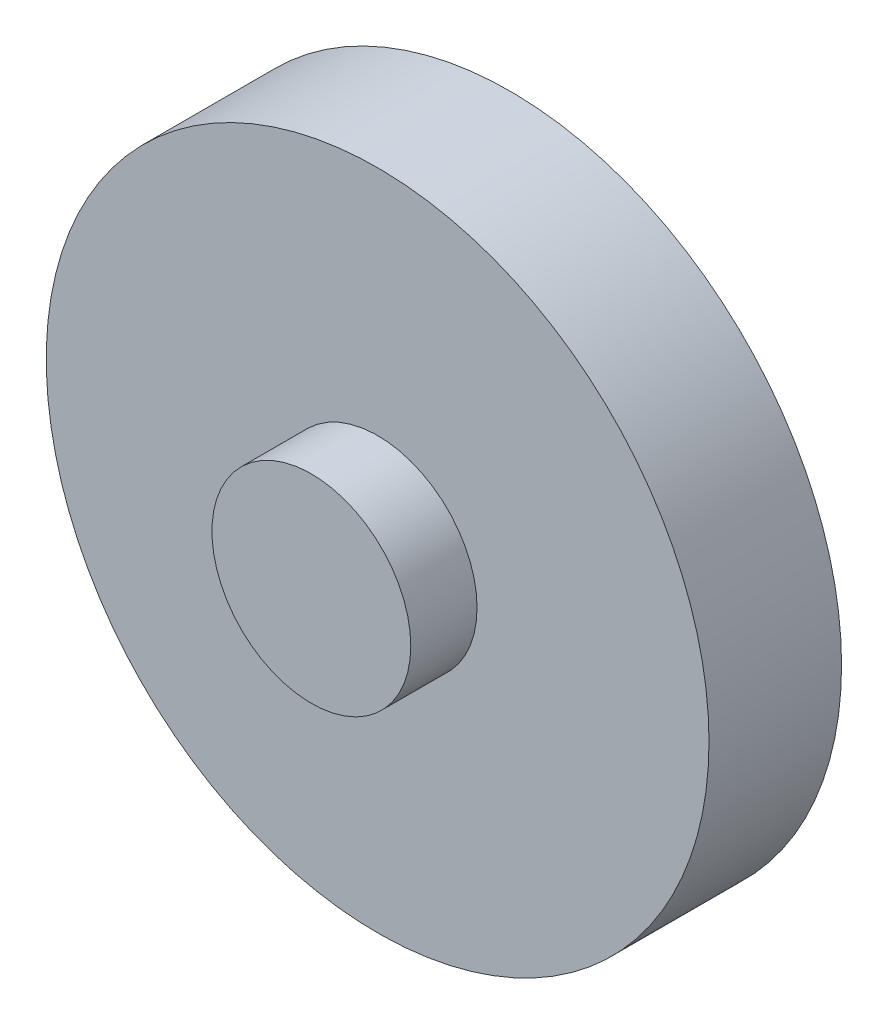
SolidWorks part; units mm, degrees
ref_plane "前视基准面" through (0, 0, 0) normal (0, 0, 1) x (1, 0, 0)
ref_plane "上视基准面" through (0, 0, 0) normal (0, 1, 0) x (1, 0, 0)
ref_plane "右视基准面" through (0, 0, 0) normal (1, 0, 0) x (0, 0, -1)
other "Configuration Table"
sketch "Sketch1" plane through (0, 0, 0) normal (0, 0, 1) x (1, 0, 0)
  circle A0 centre (0, 0) radius 50
extrude "Boss-Extrude1" add sketch "Sketch1" along normal blind 20
ref_plane "Plane1" through (0, 0, 20) normal (0, 0, 1) x (1, 0, 0)
sketch "Sketch2" plane through (0, 0, 20) normal (0, 0, 1) x (1, 0, 0)
  circle A0 centre (0, 0) radius 15
extrude "Boss-Extrude2" add sketch "Sketch2" along normal blind 10
ref_plane "bottom_face" through (0, 0, 0) normal (0, 0, 1) x (1, 0, 0)
ref_plane "top_mount_face" through (0, 0, 30) normal (0, 0, 1) x (1, 0, 0)
sketch3d "3DSketch1"
  line L0 (0, 0, 0) -> (0, 0, 100) construction
ref_axis "central_axis_z" through (0, 0, 0) along (0, 0, 1)
